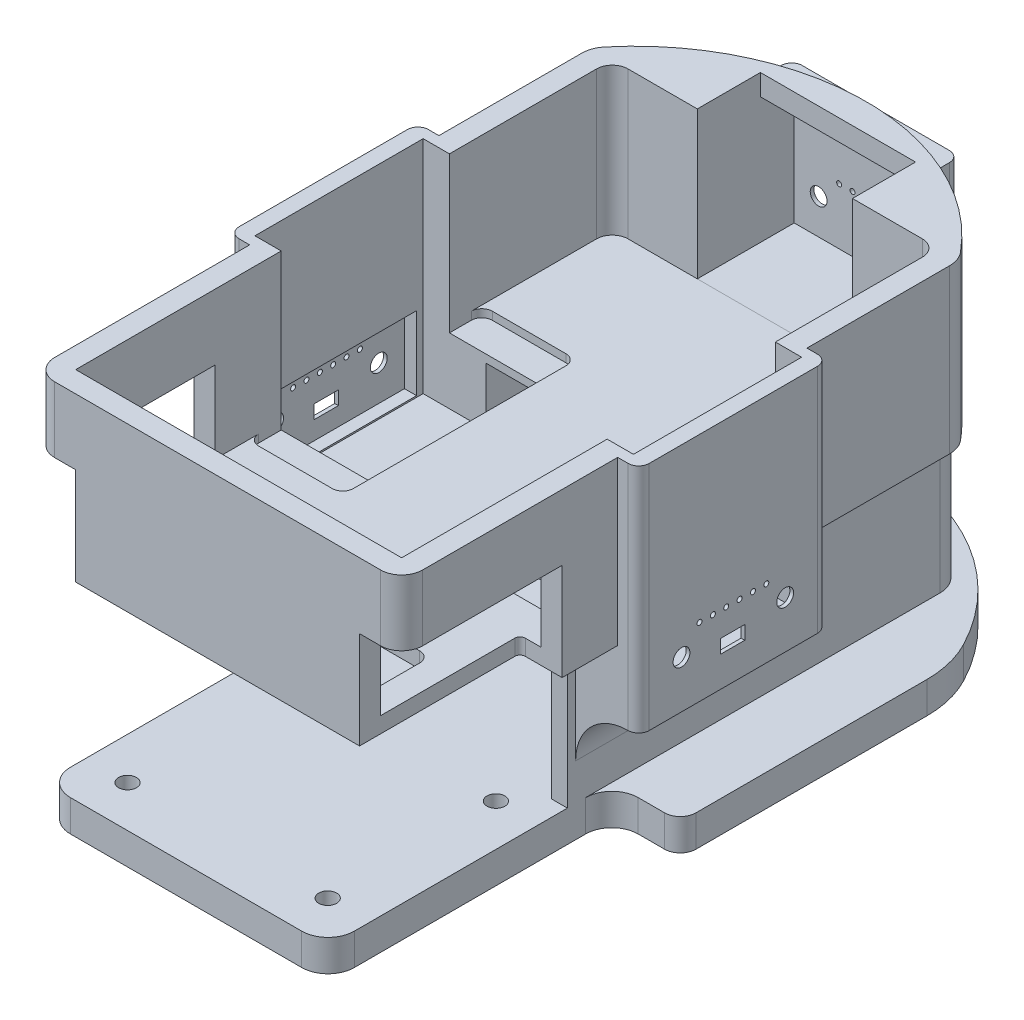
SolidWorks part; units mm, degrees
ref_plane "Plano frontal" through (0, 0, 0) normal (0, 0, 1) x (1, 0, 0)
ref_plane "Plano superior" through (0, 0, 0) normal (0, 1, 0) x (1, 0, 0)
ref_plane "Plano direito" through (0, 0, 0) normal (1, 0, 0) x (0, 0, -1)
sketch "Esboço4" plane through (0, 0, 0) normal (0, 1, 0) x (1, 0, 0)
  line L1 (-55, -54.8676) -> (25, -54.8676) construction
  line L2 (-55, -54.8676) -> (-55, 0.1324) construction
  line L3 (-55, 0.1324) -> (25, 0.1324) construction
  line L4 (25, -54.8676) -> (25, 0.1324) construction
  line L7 (-55, -98.8676) -> (25, -98.8676)
  line L8 (-55, -98.8676) -> (-55, 0.1324)
  line L10 (25, -98.8676) -> (25, 0.1324)
  line L11 (-15, 28.1324) -> (-15, -98.8676) construction
  arc A0 (-55, 0.1324) -> (25, 0.1324) centre (-15, -14.4391) cw
  point P0 (0, 0)
  dimension "D1" = 80
  dimension "D2" = 127
  dimension "D3" = 44
  dimension "D9" = 55
extrude "Ressalto-extrusão2" add sketch "Esboço4" against normal blind 6 contours L8 A0 L10 L7
sketch "Esboço5" plane through (0, 0, 0) normal (0, 1, 0) x (1, 0, 0)
  line L1 (9, -59.3376) -> (12, -59.3376)
  line L8 (-15, 28.1324) -> (-15, -110.1749) construction
  line L9 (12, -59.3376) -> (12, 16.5324)
  line L10 (12, 16.5324) -> (-42, 16.5324)
  line L11 (-42, 16.5324) -> (-42, -59.3376)
  line L12 (-42, -59.3376) -> (-39, -59.3376)
  line L13 (-39, -59.3376) -> (-39, 13.5324)
  line L14 (-39, 13.5324) -> (9, 13.5324)
  line L15 (9, 13.5324) -> (9, -59.3376)
  line L16 (-55, -98.8676) -> (25, -98.8676) construction
  line L18 (-55, -98.8676) -> (-55, 0.1324) construction
  arc A0 (25, 0.1324) -> (-55, 0.1324) centre (-15, -14.4391) ccw construction
  dimension "D1" = 3
  dimension "D2" = 3
  dimension "D3" = 115.4
  dimension "D4" = 3
  dimension "D5" = 48
  dimension "D6" = 13
  dimension "D7" = 75.87
extrude "Ressalto-extrusão3" add sketch "Esboço5" along normal blind 30
sketch "Esboço11" plane through (0, 30, 0) normal (0, 1, 0) x (1, 0, 0)
  line L3 (-50, 7.1324) -> (-15, 7.1324) construction
  line L7 (-15, -30.3676) -> (-15, -68.5788) construction
  line L13 (-42, -92.8676) -> (-42, -98.8676)
  line L14 (-42, -98.8676) -> (12, -98.8676)
  line L16 (12, -92.8676) -> (12, -98.8676)
  line L18 (-15, 28.1324) -> (-15, -108.0495) construction
  line L19 (-42, 16.5324) -> (-42, -59.3376) construction
  line L20 (-55, -98.8676) -> (25, -98.8676) construction
  line L21 (-50, 7.1324) -> (-50, -92.8676)
  line L22 (-42, -92.8676) -> (-50, -92.8676)
  line L23 (20, 7.1324) -> (20, -92.8676)
  line L24 (20, -92.8676) -> (12, -92.8676)
  line L25 (31.7419, -92.8676) -> (31.7419, 7.1324) construction
  line L26 (-15, -98.8676) -> (-15, 17.1324) construction
  arc A1 (25, 0.1324) -> (-55, 0.1324) centre (-15, -14.4391) ccw construction
  arc A2 (-50, 7.1324) -> (20, 7.1324) centre (-15, -19.5241) cw
  dimension "D1" = 68.5
  dimension "D2" = 100
  dimension "D3" = 116
  dimension "D4" = 35
  dimension "D5" = 6
extrude "Ressalto-extrusão4" add sketch "Esboço11" along normal blind 3
sketch "Esboço15" plane through (0, 33, 0) normal (0, 1, 0) x (1, 0, 0)
  line L9 (-46, -68.3394) -> (-50, 7.1324) construction
  line L11 (-50, 7.1324) -> (-50, -92.8676) construction
  line L13 (-46, 7.1998) -> (-46, -68.3394)
  line L14 (-50, -68.3394) -> (-50, 7.1324)
  line L15 (-50, -68.3394) -> (-46, -68.3394)
  line L16 (-15, 24.471) -> (-15, -143.5394) construction
  line L21 (19.0465, -92.8676) -> (19.0465, -75.5476) construction
  line L23 (-46, 7.1998) -> (16, 7.1998)
  line L26 (20, 7.1324) -> (20, -68.3394)
  line L27 (20, -92.8676) -> (20, 7.1324) construction
  line L29 (16, 7.1998) -> (16, -68.3394)
  line L30 (16, -68.3394) -> (20, -68.3394)
  arc A0 (20, 7.1324) -> (-50, 7.1324) centre (-15, -19.5241) ccw construction
  arc A1 (-50, 7.1324) -> (20, 7.1324) centre (-15, -19.5241) cw
  dimension "D1" = 17.32
  dimension "D2" = 4
extrude "Ressalto-extrusão7" add sketch "Esboço15" along normal blind 28
fillet "Filete1" radius 20 1 edges at (-55, -3, -0.1324) type face fillet first side face at (-55, -3, 49.3676) second side face at (-15, -3, -14.1324)
fillet "Filete2" radius 20 1 edges at (25, -3, -0.1324) type face fillet first side face at (25, -3, 49.3676) second side face at (-13.0197, -3, -15.3761)
sketch "Esboço22" plane through (0, 33, 0) normal (0, 1, 0) x (1, 0, 0)
  line L0 (-42, -94.8676) -> (12, -94.8676)
  line L1 (12, -94.8676) -> (12, -98.8676)
  line L2 (12, -98.8676) -> (-42, -98.8676)
  line L3 (-42, -98.8676) -> (-42, -94.8676)
  dimension "D1" = 4
extrude "Ressalto-extrusão8" add sketch "Esboço22" along normal blind 28
sketch "Esboço24" plane through (0, 0, 0) normal (0, 1, 0) x (1, 0, 0)
  line L0 (-55, -98.8676) -> (-55, -50.8676)
  line L1 (-55, -98.8676) -> (-55, -3.9763) construction
  line L2 (-55, -50.8676) -> (-42, -50.8676)
  line L3 (-42, -50.8676) -> (-42, -98.8676)
  line L4 (-55, -98.8676) -> (25, -98.8676) construction
  line L5 (-42, -98.8676) -> (-55, -98.8676)
  line L6 (-15, -98.8676) -> (-15, 24.4013) construction
  line L7 (12, -50.8676) -> (12, -98.8676)
  line L8 (25, -50.8676) -> (12, -50.8676)
  line L9 (25, -98.8676) -> (25, -50.8676)
  line L10 (12, -98.8676) -> (25, -98.8676)
  line L11 (-42, 16.5324) -> (-42, -59.3376) construction
  dimension "D2" = 48
extrude "Corte-extrusão5" cut sketch "Esboço24" against normal blind 6
fillet "Filete12" radius 5 1 edges at (-42, -3, 50.8676) type face fillet first side face at (-42, 6, 48.1351) second side face at (-48.5, -3, 50.8676)
fillet "Filete13" radius 3 1 edges at (-55, -3, 50.8676) type face fillet first side face at (-51, -3, 50.8676) second side face at (-55, -3, 27.422)
fillet "Filete14" radius 5 1 edges at (12, -3, 50.8676) type face fillet first side face at (18.5, -3, 50.8676) second side face at (12, 6, 48.1351)
fillet "Filete15" radius 3 1 edges at (25, -3, 50.8676) type face fillet first side face at (25, -3, 27.422) second side face at (21, -3, 50.8676)
ref_plane "Plano3" through (-15, 0, 0) normal (-1, 0, 0) x (0, 0, 1)
sketch "Esboço57" plane through (0, -6, 0) normal (0, -1, 0) x (-1, 0, 0)
  line L0 (15, -15.4) -> (15, 15.4) construction
  line L1 (35.5, -34.8676) -> (-5.5, -34.8676)
  line L2 (35.5, -34.8676) -> (35.5, 6.1324)
  line L3 (35.5, 6.1324) -> (-5.5, 6.1324)
  line L4 (-5.5, -34.8676) -> (-5.5, 6.1324)
  line L5 (35.5, -34.8676) -> (-5.5, 6.1324) construction
  line L6 (35.5, 6.1324) -> (-5.5, -34.8676) construction
  line L7 (15, 28.1324) -> (-35.47, 28.1324) construction
  line L9 (-17, -50.8676) -> (-35.47, -50.8676) construction
  line L10 (-35.47, -50.8676) -> (-35.47, 28.1324) construction
  arc A0 (52.7215, 5.2945) -> (-22.7215, 5.2945) centre (15, -14.4391) ccw construction
  point P0 (15, -14.3676)
  point P10 (15, 28.1324)
  point P11 (15, 6.1324)
  dimension "D1" = 41
  dimension "D2" = 41
  dimension "D3" = 36.5
  dimension "D4" = 79
extrude "Ressalto-extrusão10" add sketch "Esboço57" along normal blind 2
fillet "Filete23" radius 5 2 edges at (-42, 15, -16.5324) (12, 15, -16.5324)
sketch "Esboço58" plane through (0, 0, -7.1998) normal (0, 0, 1) x (1, 0, 0)
  line L0 (-29, 33) -> (-29, 46)
  line L1 (-46, 33) -> (16, 33) construction
  line L2 (-29, 46) -> (-1, 46)
  line L3 (-1, 46) -> (-1, 33)
  line L4 (-1, 33) -> (-29, 33)
  line L5 (-15, 15.4) -> (-15, -15.4) construction
  point P4 (-15, 46)
  dimension "D1" = 28
  dimension "D2" = 13
sketch "Esboço49" plane through (0, 33, 0) normal (0, 1, 0) x (1, 0, 0)
  line L0 (-46, 7.1998) -> (16, 7.1998) construction
  line L2 (-31, 26.3298) -> (1, 26.3298)
  line L3 (1, 26.3298) -> (1, 19.217)
  line L4 (1, 19.217) -> (-31, 19.217)
  line L5 (-31, 19.217) -> (-31, 26.3298)
  arc A2 (22.7215, 5.2945) -> (-52.7215, 5.2945) centre (-15, -14.4391) ccw construction
  point P13 (-15, 28.1324)
  point P14 (-15, 26.3298)
  dimension "D2" = 7.1127
  dimension "D3" = 19.13
  dimension "28" = 32
extrude "Ressalto-extrusão11" add sketch "Esboço49" along normal blind 26 and the other way blind 3
sketch "Esboço59" plane through (0, 33, 0) normal (0, 1, 0) x (1, 0, 0)
  line L0 (-50, -68.3394) -> (-50, -92.8676)
  line L1 (-50, -92.8676) -> (-42, -92.8676)
  line L2 (-42, -92.8676) -> (-42, -68.3394)
  line L3 (-42, -68.3394) -> (-50, -68.3394)
  line L4 (-15, 15.4) -> (-15, -15.4) construction
  line L5 (12, -92.8676) -> (12, -68.3394)
  line L6 (20, -92.8676) -> (12, -92.8676)
  line L7 (20, -68.3394) -> (20, -92.8676)
  line L8 (12, -68.3394) -> (20, -68.3394)
extrude "Corte-extrusão11" cut sketch "Esboço59" against normal blind 3
fillet "Filete27" radius 1 1 edges at (12, 31.5, 68.3394)
fillet "Filete28" radius 1 1 edges at (-42, 31.5, 68.3394)
fillet "Filete30" radius 5 1 edges at (20, 45.5, -7.1324)
fillet "Filete31" radius 5 1 edges at (-50, 45.5, -7.1324)
fillet "Filete33" radius 3 1 edges at (-46, 47, -7.1998)
sketch "Esboço61" plane through (0, 61, 0) normal (0, 1, 0) x (1, 0, 0)
  line L2 (20, -68.3394) -> (20, -98.8676)
  line L3 (20, -98.8676) -> (12, -98.8676)
  line L4 (16, -68.3394) -> (20, -68.3394) construction
  line L9 (16, -68.3394) -> (16, -94.8676)
  line L10 (16, -94.8676) -> (12, -94.8676)
  line L11 (12, -94.8676) -> (12, -98.8676)
  line L12 (16, -68.3394) -> (20, -68.3394)
  line L13 (-15, 15.4) -> (-15, -15.4) construction
  line L14 (-46, -68.3394) -> (-46, -94.8676)
  line L15 (-46, -94.8676) -> (-42, -94.8676)
  line L16 (-42, -94.8676) -> (-42, -98.8676)
  line L17 (-50, -98.8676) -> (-42, -98.8676)
  line L18 (-50, -68.3394) -> (-50, -98.8676)
  line L19 (-46, -68.3394) -> (-50, -68.3394)
extrude "Ressalto-extrusão13" add sketch "Esboço61" against normal blind 12.5
fillet "Filete36" radius 4 1 edges at (20, 54.75, 98.8676)
fillet "Filete37" radius 4 1 edges at (-50, 54.75, 98.8676)
sketch "Esboço78" plane through (20, 0, 0) normal (1, 0, 0) x (0, 0, -1)
  line L0 (-57.7758, 61) -> (-21.7758, 61)
  line L1 (-21.7758, 61) -> (-21.7758, 17)
  line L3 (-57.7758, 61) -> (-57.7758, 17)
  line L4 (-57.7758, 17) -> (-21.7758, 17)
  line L5 (-55.8676, -6) -> (-98.8676, -6) construction
  line L7 (-94.8676, 61) -> (5.3881, 61) construction
  dimension "D1" = 41.0918
  dimension "D2" = 36
  dimension "D3" = 23
sketch "Esboço62" plane through (20, 0, 0) normal (1, 0, 0) x (0, 0, -1)
  line L0 (-47.7744, 31.6917) -> (-31.7744, 31.6917) construction
  line L1 (-47.7744, 20.8917) -> (-31.7744, 20.8917) construction
  line L3 (-47.7744, 31.6917) -> (-47.7744, 29.0817) construction
  line L4 (-31.7744, 31.6917) -> (-31.7744, 29.0817) construction
  line L5 (-31.7744, 29.0817) -> (-29.5544, 29.0741) construction
  line L6 (-29.5544, 23.5017) -> (-31.7744, 23.5017) construction
  line L7 (-31.7744, 23.5017) -> (-31.7744, 20.8917) construction
  line L9 (-47.7744, 23.5017) -> (-47.7744, 20.8917) construction
  line L10 (-54.5208, 19.2917) -> (-25.028, 19.2917)
  line L11 (-39.7744, 31.6917) -> (-39.7744, 20.8917) construction
  line L12 (-49.9944, 23.5017) -> (-47.7744, 23.5017) construction
  line L13 (-47.7744, 29.0817) -> (-49.9944, 29.0741) construction
  line L14 (-52.9208, 26.2879) -> (-52.9208, 1.5479) construction
  line L15 (-54.5208, 19.2917) -> (-54.5208, 33.2917)
  line L16 (-54.5208, 33.2917) -> (-25.028, 33.2917)
  line L17 (-25.028, 33.2917) -> (-25.028, 19.2917)
  line L19 (-94.8676, 61) -> (5.3881, 61) construction
  line L21 (-29.5544, 23.4984) -> (-50.1313, 23.4984) construction
  line L23 (-29.5544, 23.4984) -> (-51.8384, 23.4984) construction
  line L24 (-23.5489, 24.0817) -> (-9.8723, 24.0817) construction
  arc A0 (-29.5544, 29.0741) -> (-29.5544, 23.5017) centre (-29.4176, 26.2879) cw construction
  arc A2 (-49.9944, 29.0741) -> (-49.9944, 23.5017) centre (-50.1313, 26.2879) ccw construction
  point P16 (-52.9208, 26.2879)
  point P24 (-26.628, 26.2879)
  dimension "D2" = 2.7895
  dimension "D16" = 7.0038
  dimension "D3" = 16
  dimension "D4" = 2.61
  dimension "D5" = 27.7083
  dimension "D6" = 44.3468
  dimension "D7" = 2.61
  dimension "D8" = 1.6
  dimension "D9" = 5.58
  dimension "D10" = 1.6
  dimension "D11" = 2.22
  dimension "D12" = 2.22
  dimension "D13" = 10.8
  dimension "D14" = 9.21
  dimension "D15" = 5.5724
  dimension "D17" = 14
sketch "Esboço63" plane through (20, 0, 0) normal (1, 0, 0) x (0, 0, -1)
  line L0 (-39.7744, 31.6917) -> (-39.7744, 20.8917) construction
  line L1 (-47.7744, 31.6917) -> (-31.7744, 31.6917) construction
  line L2 (-47.7744, 20.8917) -> (-31.7744, 20.8917) construction
  line L3 (-47.7744, 31.6917) -> (-47.7744, 29.0817) construction
  line L4 (-42.1959, 25.3817) -> (-37.5959, 25.3817)
  line L5 (-37.5959, 25.3817) -> (-37.5959, 22.7817)
  line L6 (-42.1959, 25.3817) -> (-42.1959, 22.7817)
  line L7 (-42.1959, 22.7817) -> (-37.5959, 22.7817)
  circle A0 centre (-49.634, 25.9879) radius 1.6
  circle A2 centre (-29.9149, 25.9879) radius 1.6
  circle A3 centre (-46.2044, 30.0217) radius 0.475
  circle A4 centre (-43.6644, 30.0217) radius 0.475
  circle A5 centre (-41.1244, 30.0217) radius 0.475
  circle A6 centre (-38.5844, 30.0217) radius 0.475
  circle A7 centre (-36.0444, 30.0217) radius 0.475
  circle A8 centre (-33.5044, 30.0217) radius 0.475
  arc A11 (-29.5544, 23.5017) -> (-29.5544, 29.0741) centre (-29.4176, 26.2879) ccw construction
  point P5 (-26.628, 26.2879)
  dimension "D3" = 3.2
  dimension "D4" = 0.95
  dimension "D2" = 0.3
  dimension "D5" = 1.67
  dimension "D6" = 1.57
  dimension "D8" = 1.89
  dimension "D9" = 2.6
  dimension "D10" = 4.6
  dimension "D11" = 5.5785
  dimension "D12" = 3.2868
  dimension "D7" = 6
sketch "Esboço64" plane through (0, 0, -26.3298) normal (0, 0, -1) x (-1, 0, 0)
  line L0 (7, 45.4) -> (23, 45.4) construction
  line L1 (7, 34.6001) -> (23, 34.6001) construction
  line L2 (4.78, 37.21) -> (7, 37.21) construction
  line L3 (7, 45.4) -> (7, 42.786) construction
  line L4 (23, 45.4) -> (23, 42.0958) construction
  line L5 (23, 42.0958) -> (25.22, 42.0958) construction
  line L6 (25.22, 36.5169) -> (23, 36.5169) construction
  line L7 (23, 36.5169) -> (23, 34.6001) construction
  line L8 (7, 42.786) -> (4.78, 42.7775) construction
  line L9 (7, 37.21) -> (7, 34.6001) construction
  line L11 (15, 46) -> (15, 27.7334) construction
  line L13 (0.315, 33.0001) -> (29.8252, 33.0001)
  line L14 (0.315, 33.0001) -> (0.315, 57.0001)
  line L15 (0.315, 57.0001) -> (29.8252, 57.0001)
  line L16 (29.8252, 57.0001) -> (29.8252, 33.0001)
  line L18 (-18.8466, 30) -> (-1, 30) construction
  arc A0 (25.22, 42.0958) -> (25.22, 36.5169) centre (25.2456, 39.3064) cw construction
  arc A1 (4.78, 42.7775) -> (4.78, 37.21) centre (4.6002, 39.9937) ccw construction
  dimension "D6" = 2.7895
  dimension "D7" = 2.7895
  dimension "D1" = 16
  dimension "D2" = 2.22
  dimension "D3" = 2.22
  dimension "D4" = 2.22
  dimension "D5" = 2.22
  dimension "D9" = 29.5102
  dimension "D11" = 24
  dimension "D13" = 3.0001
sketch "Esboço66" plane through (0, 0, -26.3298) normal (0, 0, -1) x (-1, 0, 0)
  line L0 (12.5785, 39.0901) -> (17.1785, 39.0901)
  line L1 (17.1785, 39.0901) -> (17.1785, 36.4901)
  line L2 (12.5785, 39.0901) -> (12.5785, 36.4901)
  line L3 (12.5785, 36.4901) -> (17.1785, 36.4901)
  line L4 (7, 45.4) -> (23, 45.4) construction
  line L5 (7, 34.6001) -> (23, 34.6001) construction
  line L6 (15, 27.7334) -> (15, 44.5612) construction
  line L7 (15, -15.4) -> (15, 15.4) construction
  circle A0 centre (4.8222, 39.698) radius 1.6
  circle A2 centre (8.57, 43.73) radius 0.475
  arc A3 (4.78, 42.7775) -> (4.78, 37.21) centre (4.6002, 39.9937) ccw construction
  circle A4 centre (25.1778, 39.698) radius 1.6
  circle A5 centre (11.11, 43.73) radius 0.475
  circle A6 centre (13.65, 43.73) radius 0.475
  circle A7 centre (16.19, 43.73) radius 0.475
  circle A8 centre (18.73, 43.73) radius 0.475
  circle A9 centre (21.27, 43.73) radius 0.475
  point P13 (1.8107, 39.9938)
  dimension "D1" = 0.2958
  dimension "D2" = 3.0116
  dimension "D3" = 1.57
  dimension "D4" = 1.67
  dimension "D6" = 1.89
  dimension "D7" = 5.5785
  dimension "D8" = 2.6
  dimension "D9" = 4.6
  dimension "D5" = 6
extrude "Corte-extrusão15" cut sketch "Esboço66" against normal blind 1
fillet "Filete38" radius 3 1 edges at (16, 47, -7.1998)
extrude "Corte-extrusão17" cut sketch "Esboço64" along normal blind 18.43 from surface starting at face at (-15, 47, -7.1998)
fillet "Filete49" radius 2 1 edges at (1, 44.5, -26.3298)
fillet "Filete52" radius 2 1 edges at (-31, 44.5, -26.3298)
sketch "Esboço73" plane through (0, 0, 98.8676) normal (0, 0, 1) x (1, 0, 0)
  line L0 (-42, 0) -> (12, 0)
  line L1 (12, 0) -> (12, -6)
  line L2 (12, -6) -> (-42, -6)
  line L3 (-42, -6) -> (-42, 0)
extrude "Ressalto-extrusão14" add sketch "Esboço73" along normal blind 6
fillet "Filete60" radius 5 1 edges at (12, -3, 104.8676)
fillet "Filete61" radius 5 1 edges at (-42, -3, 104.8676)
sketch "Esboço77" plane through (0, -6, 0) normal (0, -1, 0) x (-1, 0, 0)
  line L0 (-12, -96.9676) -> (-4.04, -96.9676) construction
  line L1 (-12, -55.8676) -> (-12, -99.8676) construction
  line L2 (37, -104.8676) -> (-7, -104.8676) construction
  line L3 (15, -104.8676) -> (15, -101.5371) construction
  line L4 (-4.04, -96.9676) -> (-4.04, -64.9676) construction
  circle A0 centre (-4.04, -96.9676) radius 1.7
  circle A1 centre (-4.04, -64.9676) radius 1.7
  circle A2 centre (34.04, -64.9676) radius 1.7
  circle A3 centre (34.04, -96.9676) radius 1.7
  dimension "D2" = 3.4
  dimension "D5" = 3.4
  dimension "D1" = 7.96
  dimension "D3" = 7.9
  dimension "D4" = 32
extrude "Corte-extrusão25" cut sketch "Esboço77" against normal blind 6
extrude "Ressalto-extrusão16" add sketch "Esboço78" along normal blind 4
sketch "Esboço81" plane through (24, 0, 0) normal (1, 0, 0) x (0, 0, -1)
  line L0 (-57.7758, 30) -> (-21.7758, 30)
  line L1 (-21.7758, 17) -> (-21.7758, 61) construction
  line L2 (-59.3376, 30) -> (11.5324, 30) construction
  line L3 (-21.7758, 30) -> (-21.7758, 17)
  line L4 (-57.7758, 17) -> (-21.7758, 17) construction
  line L5 (-21.7758, 17) -> (-57.7758, 17)
  line L6 (-57.7758, 61) -> (-57.7758, 17) construction
  line L7 (-57.7758, 17) -> (-57.7758, 30)
  line L8 (-21.7758, 61) -> (-57.7758, 61) construction
  dimension "D1" = 31
  dimension "D2" = 13
  dimension "D3" = 36
extrude "Ressalto-extrusão17" add sketch "Esboço81" against normal blind 8 from surface starting at face at (20, 23.5, 39.7758)
extrude "Corte-extrusão29" cut sketch "Esboço62" along normal blind 3.3
extrude "Corte-extrusão30" cut sketch "Esboço63" along normal blind 4
sketch "Esboço83" plane through (0, 61, 0) normal (0, 1, 0) x (1, 0, 0)
  line L0 (21, -23.7758) -> (21, -55.7758)
  line L1 (24, -21.7758) -> (20, -21.7758) construction
  line L2 (24, -57.7758) -> (20, -57.7758) construction
  line L3 (21, -23.7758) -> (-2, -23.7758)
  line L5 (-2, -23.7758) -> (-2, -55.7758)
  line L7 (-2, -55.7758) -> (21, -55.7758)
  line L8 (24, -21.7758) -> (24, -57.7758) construction
  dimension "D1" = 2
  dimension "D2" = 2
  dimension "D3" = 3
  dimension "D4" = 23
extrude "Corte-extrusão31" cut sketch "Esboço83" against normal blind 42
sketch "Esboço86" plane through (24, 0, 0) normal (1, 0, 0) x (0, 0, -1)
  line L5 (-47.7744, 35.2062) -> (-31.8209, 35.2062)
  line L7 (-47.7744, 35.2062) -> (-47.7744, 28.5721)
  line L10 (-47.7744, 28.5721) -> (-31.8209, 28.5721)
  line L11 (-31.8209, 28.5721) -> (-31.8209, 35.2062)
  line L12 (-47.7744, 29.0817) -> (-49.9944, 29.0741) construction
  line L13 (-59.3376, 0) -> (-99.8676, 0) construction
  dimension "D1" = 0.5097
  dimension "D2" = 15.9536
  dimension "D3" = 6.6342
  dimension "D4" = 28.5721
mirror "Espelhar7" about plane through (-15, 0, 0) normal (-1, 0, 0) of "Ressalto-extrusão16"
sketch "Esboço92" plane through (-54, 0, 0) normal (-1, 0, 0) x (0, 0, 1)
  line L0 (21.7758, 30) -> (57.7758, 30)
  line L1 (57.7758, 30) -> (57.7758, 17)
  line L2 (-16.5324, 0) -> (-16.5324, 30) construction
  line L4 (57.7758, 17) -> (21.7758, 17)
  line L6 (21.7758, 17) -> (21.7758, 30)
  line L7 (21.7758, 61) -> (57.7758, 61) construction
  dimension "D1" = 36
  dimension "D2" = 13
  dimension "D3" = 31
  dimension "D4" = 38.3082
extrude "Ressalto-extrusão18" add sketch "Esboço92" against normal blind 8 from surface starting at face at (-50, 23.5, 39.7758)
mirror "Espelhar21" about plane through (-15, 0, 0) normal (-1, 0, 0) of "Corte-extrusão31", "Corte-extrusão30", "Corte-extrusão29"
sketch "Esboço93" plane through (-54, 0, 0) normal (-1, 0, 0) x (0, 0, 1)
  line L0 (30.7758, 35.2062) -> (30.7758, 28.5721)
  line L1 (30.7758, 28.5721) -> (48.7758, 28.5721)
  line L2 (48.7758, 28.5721) -> (48.7758, 35.2062)
  line L3 (48.7758, 35.2062) -> (30.7758, 35.2062)
  line L5 (3.9763, 0) -> (-5.2945, 0) construction
  line L6 (39.7758, 61) -> (39.7758, 11.0081) construction
  line L7 (21.7758, 61) -> (57.7758, 61) construction
  point P6 (39.7758, 35.2062)
  dimension "D1" = 18
  dimension "D2" = 6.6342
  dimension "D3" = 28.5721
fillet "Filete67" radius 2 2 edges at (24, 39, 57.7758) (24, 39, 21.7758)
fillet "Filete68" radius 2 2 edges at (-54, 39, 57.7758) (-54, 39, 21.7758)
sketch "Esboço96" plane through (0, 33, 0) normal (0, 1, 0) x (1, 0, 0)
  line L0 (-37.0473, -80.4776) -> (7.0473, -80.4776)
  line L1 (7.0473, -80.4776) -> (7.0473, -93.5976)
  line L2 (-37.0473, -80.4776) -> (-37.0473, -93.5976)
  line L3 (-37.0473, -93.5976) -> (7.0473, -93.5976)
  line L4 (-15, -94.8676) -> (-15, -59.2914) construction
  line L5 (16, -94.8676) -> (-46, -94.8676) construction
  line L6 (12, -94.8676) -> (-42, -94.8676) construction
  point P8 (-15, -80.4776)
  dimension "D1" = 44.0945
  dimension "D2" = 1.27
  dimension "D3" = 13.12
extrude "Corte-extrusão34" cut sketch "Esboço96" against normal blind 3
sketch "Esboço98" plane through (0, 33.0001, 0) normal (0, 1, 0) x (1, 0, 0)
  line L0 (-29.8252, 19.1998) -> (-29.8252, 7.1998)
  line L1 (-29.8252, 7.1998) -> (-0.315, 7.1998)
  line L2 (-0.315, 25.6298) -> (-0.315, 7.1998) construction
  line L3 (-0.315, 7.1998) -> (-29.8252, 7.1998) construction
  line L4 (-0.315, 7.1998) -> (-0.315, 19.1998)
  line L5 (-0.315, 19.1998) -> (-29.8252, 19.1998)
  dimension "D1" = 12
extrude "Corte-extrusão37" cut sketch "Esboço98" along normal blind 28
fillet "Filete69" radius 10 1 edges at (12, 17, 39.7758) type face fillet first side face at (12, 11.8333, 47.182) second side face at (19.4714, 17, 39.7758)
fillet "Filete70" radius 10 1 edges at (-42, 17, 39.7758) type face fillet first side face at (-49.4714, 17, 39.7758) second side face at (-42, 11.8333, 47.182)
fillet "Filete72" radius 5 1 edges at (-15, 30, -16.5324) type face fillet first side face at (-15, 30, -8.1429) second side face at (-15, 15, -16.5324)
fillet "Filete77" radius 2 4 edges at (7.0473, 31.5, 80.4776) (7.0473, 31.5, 93.5976) (-37.0473, 31.5, 80.4776) (-37.0473, 31.5, 93.5976)
sketch "Esboço107" plane through (0, 33, 0) normal (0, 1, 0) x (1, 0, 0)
  line L0 (16, -55.7758) -> (16, -62.0576)
  line L1 (16, -55.7758) -> (16, -68.3394) construction
  line L2 (16, -62.0576) -> (-2, -55.7758) construction
  line L3 (-2, -55.7758) -> (-2, -62.0576)
  line L4 (-2, -62.0576) -> (16, -62.0576)
  line L5 (-2, -55.7758) -> (16, -55.7758)
  line L6 (-2, -23.7758) -> (-2, -17.6187)
  line L7 (-2, -17.6187) -> (16, -17.6187)
  line L8 (16, 4.1998) -> (16, -23.7758) construction
  line L9 (16, -23.7758) -> (16, -17.6187)
  line L10 (-2, -23.7758) -> (16, -23.7758)
  line L11 (-15, 15.3866) -> (-15, -15.3866) construction
  line L12 (-28, -55.7758) -> (-28, -62.0576)
  line L13 (-28, -62.0576) -> (-46, -62.0576)
  line L14 (-46, -55.7758) -> (-46, -62.0576)
  line L15 (-28, -55.7758) -> (-46, -55.7758)
  line L16 (-28, -23.7758) -> (-28, -17.6187)
  line L17 (-28, -17.6187) -> (-46, -17.6187)
  line L18 (-46, -23.7758) -> (-46, -17.6187)
  line L19 (-28, -23.7758) -> (-46, -23.7758)
extrude "Corte-extrusão45" cut sketch "Esboço107" against normal blind 1.5
fillet "Filete83" radius 2 8 edges at (-28, 32.25, 62.0576) (16, 32.25, 62.0576) (-2, 32.25, 62.0576) (-46, 32.25, 62.0576) (-28, 32.25, 17.6187) (16, 32.25, 17.6187) (-2, 32.25, 17.6187) (-46, 32.25, 17.6187)
